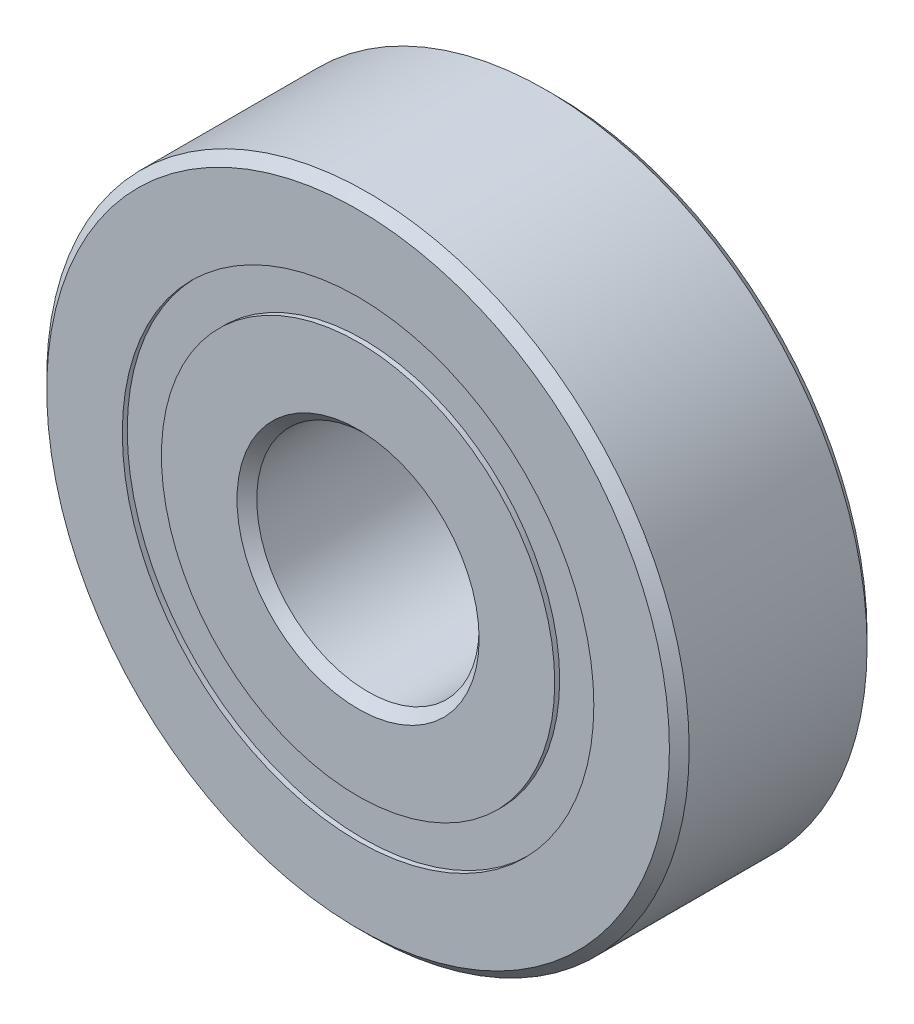
SolidWorks part; units mm, degrees
ref_plane "Front Plane" through (0, 0, 0) normal (0, 0, 1) x (1, 0, 0)
ref_plane "Top Plane" through (0, 0, 0) normal (0, 1, 0) x (1, 0, 0)
ref_plane "Right Plane" through (0, 0, 0) normal (1, 0, 0) x (0, 0, -1)
sketch "Sketch1" plane through (0, 0, 0) normal (1, 0, 0) x (0, 0, -1)
  line L0 (-4, 0) -> (4, 0) construction
  line L1 (0, 13) -> (0, -13) construction
  line L2 (3.6, 13) -> (-3.6, 13)
  line L3 (-3.6, 13) -> (-4, 12.6)
  line L4 (-4, 12.6) -> (-4, 9.5412)
  line L5 (-4, 9.5412) -> (-1.7778, 9.5412)
  line L6 (4, 9.5412) -> (1.7778, 9.5412)
  line L7 (4, 12.6) -> (4, 9.5412)
  line L8 (3.6, 13) -> (4, 12.6)
  line L9 (0, 13) -> (0, 8.75) construction
  line L10 (0, 8.75) -> (0, 4.5) construction
  arc A0 (-1.7778, 9.5412) -> (1.7778, 9.5412) centre (0, 8.75) cw
  point P14 (0, 4.5)
  dimension "Width" = 8
  dimension "OD" = 26
  dimension "D1" = 45
  dimension "D2" = 0.4
  dimension "Shaft Dia" = 9
  dimension "D3" = 3.5556
  dimension "D4" = 0.7912
revolve "Revolve1" add sketch "Sketch1" angle 360 about L0
sketch "Sketch3" plane through (0, 0, 0) normal (1, 0, 0) x (0, 0, -1)
  line L0 (-4, 7.9588) -> (-1.7778, 7.9588)
  line L1 (0, 13) -> (0, -13) construction
  line L2 (-4, 12.6) -> (-4, 9.5412) construction
  line L3 (-4, 7.9588) -> (-4, 4.9)
  line L4 (-3.6, 13) -> (-4, 12.6) construction
  line L5 (-4, 4.9) -> (-3.6, 4.5)
  line L6 (-3.6, 4.5) -> (3.6, 4.5)
  line L7 (3.6, 13) -> (3.6, -13) construction
  line L8 (3.6, 4.5) -> (4, 4.9)
  line L9 (4, -12.6) -> (4, 12.6) construction
  line L10 (4, 4.9) -> (4, 7.9588)
  line L11 (4, 7.9588) -> (1.7778, 7.9588)
  line L13 (3.6, 13) -> (4, 12.6) construction
  arc A0 (1.7778, 9.5412) -> (-1.7778, 9.5412) centre (0, 8.75) ccw construction
  arc A1 (1.7778, 7.9588) -> (-1.7778, 7.9588) centre (0, 8.75) cw
revolve "Revolve3" add sketch "Sketch3" angle 360 about L0
sketch "Sketch4" plane through (0, 0, 0) normal (1, 0, 0) x (0, 0, -1)
  line L0 (-1.9459, 8.75) -> (1.9459, 8.75)
  arc A2 (-1.9459, 8.75) -> (1.9459, 8.75) centre (0, 8.75) cw
  arc A3 (1.7778, 9.5412) -> (-1.7778, 9.5412) centre (0, 8.75) ccw construction
revolve "Revolve4" add sketch "Sketch4" angle 360 about L0
ref_axis "Axis1" through (0, 0, -4) along (0, 0, 1)
pattern_circular "CirPattern1" count 12 every 30 about axis through (0, 0, -4) along (0, 0, 1) of bodies 104
sketch "Sketch5" plane through (0, 0, 0) normal (1, 0, 0) x (0, 0, -1)
  line L0 (-4, 9.5412) -> (-1.7778, 9.5412) construction
  line L1 (-3.8, 9.5412) -> (-1.9459, 9.5412)
  line L2 (-3.8, 9.5412) -> (-3.8, 7.9588)
  line L3 (-3.8, 7.9588) -> (-1.9459, 7.9588)
  line L4 (-1.9459, 9.5412) -> (-1.9459, 7.9588)
  line L5 (-4, 7.9588) -> (-1.7778, 7.9588) construction
  line L6 (4, 9.5412) -> (1.7778, 9.5412) construction
  line L7 (3.8, 9.5412) -> (1.9459, 9.5412)
  line L8 (3.8, 9.5412) -> (3.8, 7.9588)
  line L9 (3.8, 7.9588) -> (1.9459, 7.9588)
  line L10 (1.9459, 9.5412) -> (1.9459, 7.9588)
  line L11 (4, 7.9588) -> (1.7778, 7.9588) construction
  line L12 (-3.6, 13) -> (-4, 12.6) construction
  point P18 (-3.8, 12.8)
revolve "Revolve5" add sketch "Sketch5" angle 360 about L0
equation "\"D2@Sketch1\" = \"Width@Sketch1\"*.05"
equation "\"D3@Sketch1\" = \"Width@Sketch1\"/2.25"
equation "\"D4@Sketch1\" = (((\"OD@Sketch1\"-\"Width@Sketch1\")/2)/3.25)/3.5"
equation "\"D2@CirPattern1\" = 360/\"Balls@CirPattern1\""
